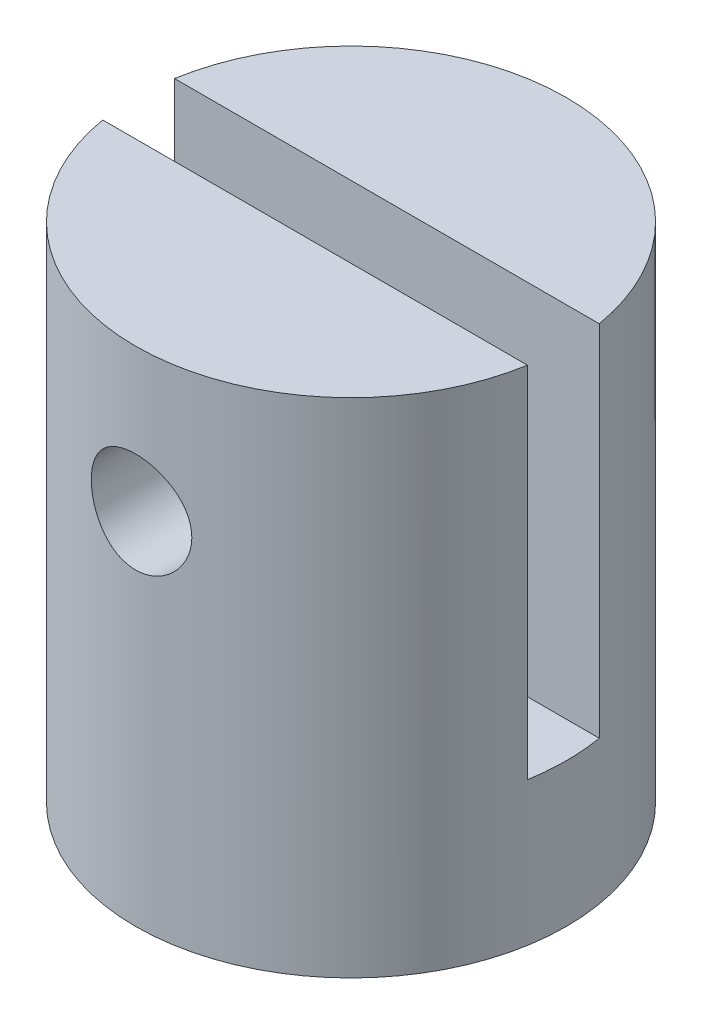
SolidWorks part; units mm, degrees
ref_plane "Front Plane" through (0, 0, 0) normal (0, 0, 1) x (1, 0, 0)
ref_plane "Top Plane" through (0, 0, 0) normal (0, 1, 0) x (1, 0, 0)
ref_plane "Right Plane" through (0, 0, 0) normal (1, 0, 0) x (0, 0, -1)
sketch "Sketch1" plane through (0, 0, 0) normal (0, 0, 1) x (1, 0, 0)
  line L0 (0, -17.5) -> (0, 17.5) construction
  line L5 (0, 17.5) -> (15, 17.5)
  line L6 (15, 17.5) -> (15, -17.5)
  line L7 (15, -17.5) -> (0, -17.5)
  line L8 (0, 17.5) -> (0, -17.5)
  point P12 (15, 0)
  dimension "D1" = 30
  dimension "D2" = 35
revolve "Revolve1" add sketch "Sketch1" angle 360 about L0
sketch "Sketch2" plane through (0, -17.5, 0) normal (0, -1, 0) x (1, 0, 0)
  circle A0 centre (0, 0) radius 5
  dimension "D1" = 10
extrude "Boss-Extrude2" add sketch "Sketch2" along normal blind 5 contours A0
sketch "Sketch4" plane through (0, 0, 0) normal (0, 0, 1) x (1, 0, 0)
  line L1 (-15, -7.5) -> (15, -7.5)
  line L2 (-15, -7.5) -> (-15, 17.5)
  line L3 (-15, 17.5) -> (15, 17.5)
  line L4 (15, -7.5) -> (15, 17.5)
  line L5 (-15, -7.5) -> (15, 17.5) construction
  line L6 (-15, 17.5) -> (15, -7.5) construction
  point P0 (0, 5)
  dimension "D1" = 25
extrude "Cut-Extrude1" cut sketch "Sketch4" against normal mid plane 5
sketch "Sketch5" plane through (0, 0, 0) normal (0, 0, 1) x (1, 0, 0)
  circle A0 centre (0, 7.5) radius 3.5
  dimension "D1" = 7
  dimension "D2" = 15
extrude "Cut-Extrude2" cut sketch "Sketch5" against normal through all both and the other way through all
